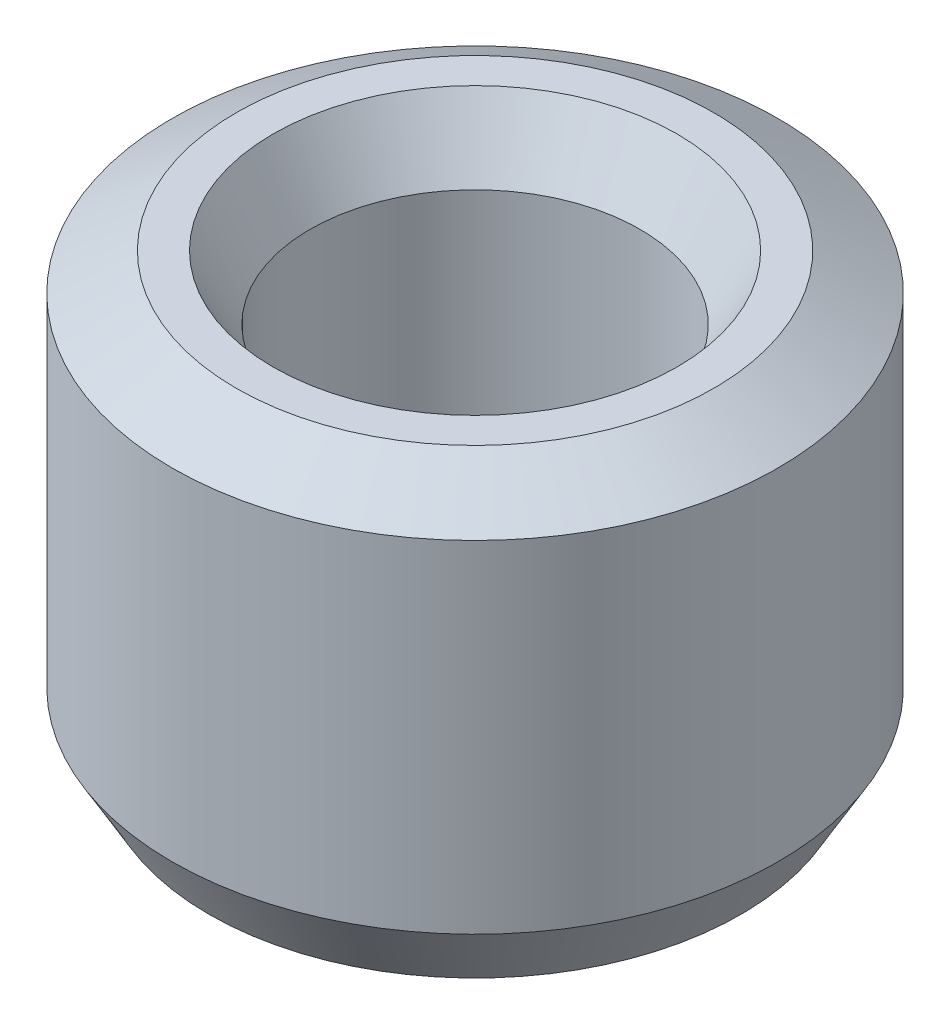
SolidWorks part; units mm, degrees
ref_plane "Front Plane" through (0, 0, 0) normal (0, 0, 1) x (1, 0, 0)
ref_plane "Top Plane" through (0, 0, 0) normal (0, 1, 0) x (1, 0, 0)
ref_plane "Right Plane" through (0, 0, 0) normal (1, 0, 0) x (0, 0, -1)
sketch "Sketch1" plane through (0, 0, 0) normal (0, 1, 0) x (1, 0, 0)
  circle A0 centre (0, 0) radius 32.5
  dimension "SLEEVE_OD" = 65
extrude "Boss-Extrude1" add sketch "Sketch1" along normal blind 47.4426
sketch "Sketch2" plane through (0, 0, 0) normal (0, 1, 0) x (1, 0, 0)
  circle A0 centre (0, 0) radius 17.7004
  dimension "BORE_D" = 35.4007
extrude "Cut-Extrude1" cut sketch "Sketch2" along normal through all
chamfer "Chamfer1" distance 3.9702 angle 60 4 edges at (0, 47.4426, 17.7004) (0, 0, 17.7004) (0, 0, 32.5) (0, 47.4426, 32.5) first distance on face at (0, 47.4426, 17.7004) first distance on face at (0, 0, 17.7004) first distance on face at (0, 47.4426, 32.5)
